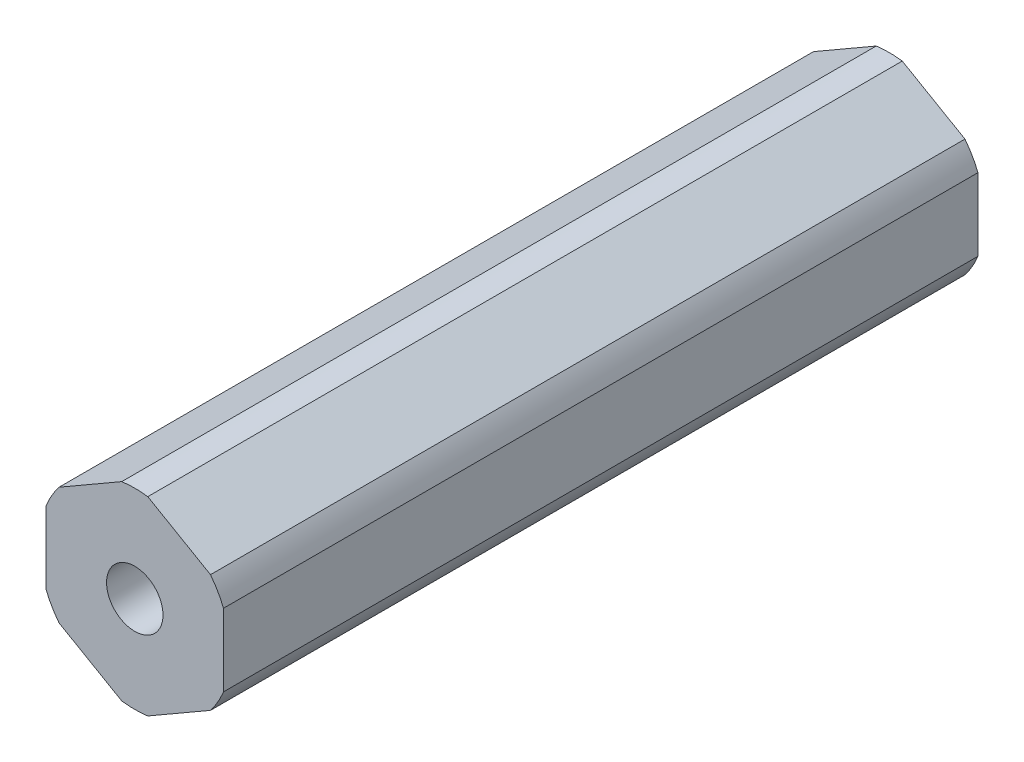
SolidWorks part; units mm, degrees
material "6061-T6 (SS)"
ref_plane "Front Plane" through (0, 0, 0) normal (0, 0, 1) x (1, 0, 0)
ref_plane "Top Plane" through (0, 0, 0) normal (0, 1, 0) x (1, 0, 0)
ref_plane "Right Plane" through (0, 0, 0) normal (1, 0, 0) x (0, 0, -1)
sketch "Sketch1" plane through (0, 0, 0) normal (0, 0, 1) x (1, 0, 0)
  line L1 (0, 7.3323) -> (-6.35, 3.6662)
  line L2 (-6.35, 3.6662) -> (-6.35, -3.6662)
  line L3 (-6.35, -3.6662) -> (0, -7.3323)
  line L4 (0, -7.3323) -> (6.35, -3.6662)
  line L5 (6.35, -3.6662) -> (6.35, 3.6662)
  line L6 (6.35, 3.6662) -> (0, 7.3323)
  circle A0 centre (0, 0) radius 6.858
  circle A1 centre (0, 0) radius 6.35 construction
  dimension "D1" = 12.7
  dimension "D2" = 13.716
extrude "Boss-Extrude1" add sketch "Sketch1" along normal mid plane 53.975 contours L5 A0 L6 L1 L2 L3 L4 region at (0, 0, 0)
sketch "Sketch2" plane through (0, 0, 26.9875) normal (0, 0, 1) x (1, 0, 0)
  circle A0 centre (0, 0) radius 2.0193
  dimension "D1" = 4.0386
extrude "Cut-Extrude1" cut sketch "Sketch2" against normal through all
